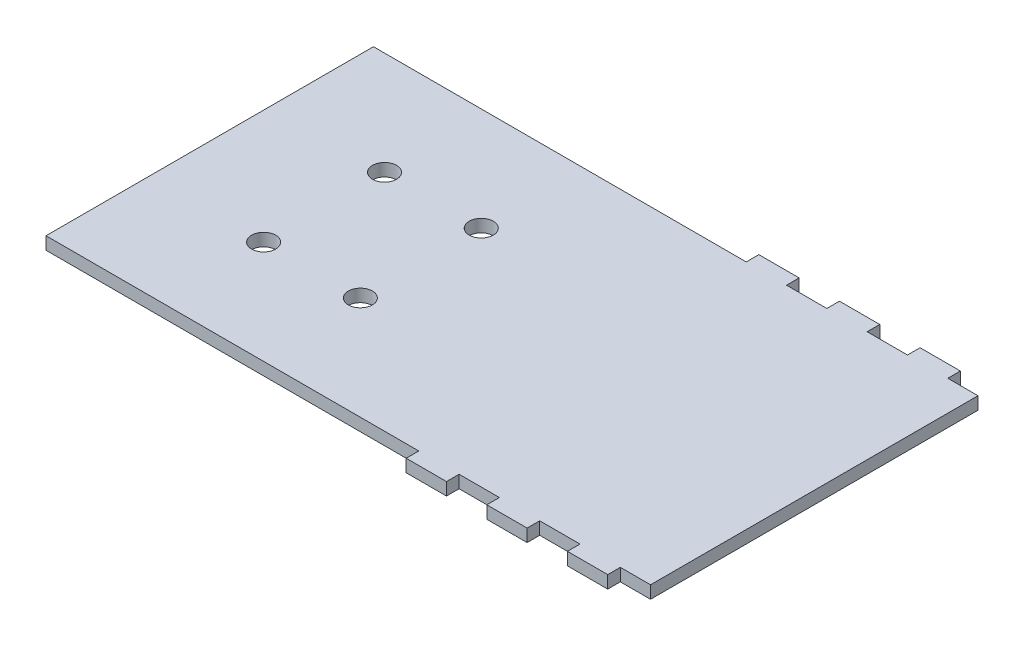
SolidWorks part; units mm, degrees
ref_plane "Front Plane" through (0, 0, 0) normal (0, 0, 1) x (1, 0, 0)
ref_plane "Top Plane" through (0, 0, 0) normal (0, 1, 0) x (1, 0, 0)
ref_plane "Right Plane" through (0, 0, 0) normal (1, 0, 0) x (0, 0, -1)
sketch "Sketch1" plane through (0, 0, 0) normal (0, 1, 0) x (1, 0, 0)
  line L0 (38.1, -41.275) -> (48.26, -41.275)
  line L1 (76.2, -41.275) -> (-76.2, -41.275)
  line L2 (76.2, -41.275) -> (76.2, 41.275)
  line L3 (76.2, 41.275) -> (-76.2, 41.275)
  line L4 (-76.2, -41.275) -> (-76.2, 41.275)
  line L5 (76.2, -41.275) -> (-76.2, 41.275) construction
  line L6 (76.2, 41.275) -> (-76.2, -41.275) construction
  line L7 (58.42, -41.275) -> (68.58, -41.275)
  line L8 (58.42, -41.275) -> (58.42, -44.45)
  line L9 (58.42, -44.45) -> (68.58, -44.45)
  line L10 (68.58, -41.275) -> (68.58, -44.45)
  line L11 (38.1, -41.275) -> (38.1, -44.45)
  line L12 (38.1, -44.45) -> (48.26, -44.45)
  line L13 (48.26, -41.275) -> (48.26, -44.45)
  line L14 (17.78, -41.275) -> (27.94, -41.275)
  line L15 (17.78, -41.275) -> (17.78, -44.45)
  line L16 (17.78, -44.45) -> (27.94, -44.45)
  line L17 (27.94, -41.275) -> (27.94, -44.45)
  line L18 (58.42, 44.45) -> (68.58, 44.45)
  line L19 (58.42, 44.45) -> (58.42, 41.275)
  line L20 (58.42, 41.275) -> (68.58, 41.275)
  line L21 (68.58, 44.45) -> (68.58, 41.275)
  line L22 (38.1, 44.45) -> (48.26, 44.45)
  line L23 (38.1, 44.45) -> (38.1, 41.275)
  line L24 (38.1, 41.275) -> (48.26, 41.275)
  line L25 (48.26, 44.45) -> (48.26, 41.275)
  line L26 (17.78, 44.45) -> (27.94, 44.45)
  line L27 (17.78, 44.45) -> (17.78, 41.275)
  line L28 (17.78, 41.275) -> (27.94, 41.275)
  line L29 (27.94, 44.45) -> (27.94, 41.275)
  line L30 (58.42, -41.275) -> (38.1, -41.275) construction
  point P0 (0, 0)
  dimension "D1" = 3.175
  dimension "D2" = 10.16
  dimension "D5" = 20.32
  dimension "D6" = 82.55
  dimension "D7" = 152.4
  dimension "D8" = 7.62
  dimension "D3" = 3
  dimension "D4" = 2
extrude "Boss-Extrude1" add sketch "Sketch1" along normal blind 3.175 contours L17 L1 L15 L16 | L4 L1 L0 L2 L3 | L13 L0 L11 L12 | L29 L26 L27 L3 | L10 L9 L8 L7 | L18 L21 L20 L19 | L22 L25 L24 L23 region at (0, 0, 0) region at (43.18, 0, 42.8625) region at (22.86, 0, 42.8625) region at (22.86, 0, -42.8625)
sketch "Sketch2" plane through (0, 3.175, 0) normal (0, 1, 0) x (1, 0, 0)
  line L0 (-47.3754, 15.24) -> (-47.3754, -15.24) construction
  line L1 (-47.3754, 0) -> (-76.2, 0) construction
  line L2 (-76.2, -41.275) -> (-76.2, 41.275) construction
  circle A0 centre (-47.3754, 15.24) radius 3.039
  circle A1 centre (-22.9914, 15.24) radius 3.039
  circle A2 centre (-22.9914, -15.24) radius 3.039
  circle A3 centre (-47.3754, -15.24) radius 3.039
  dimension "D4" = 24.384
  dimension "D3" = 30.48
  dimension "D1" = 2
  dimension "D2" = 2
extrude "Caster Mounting Holes" cut sketch "Sketch2" against normal through all
